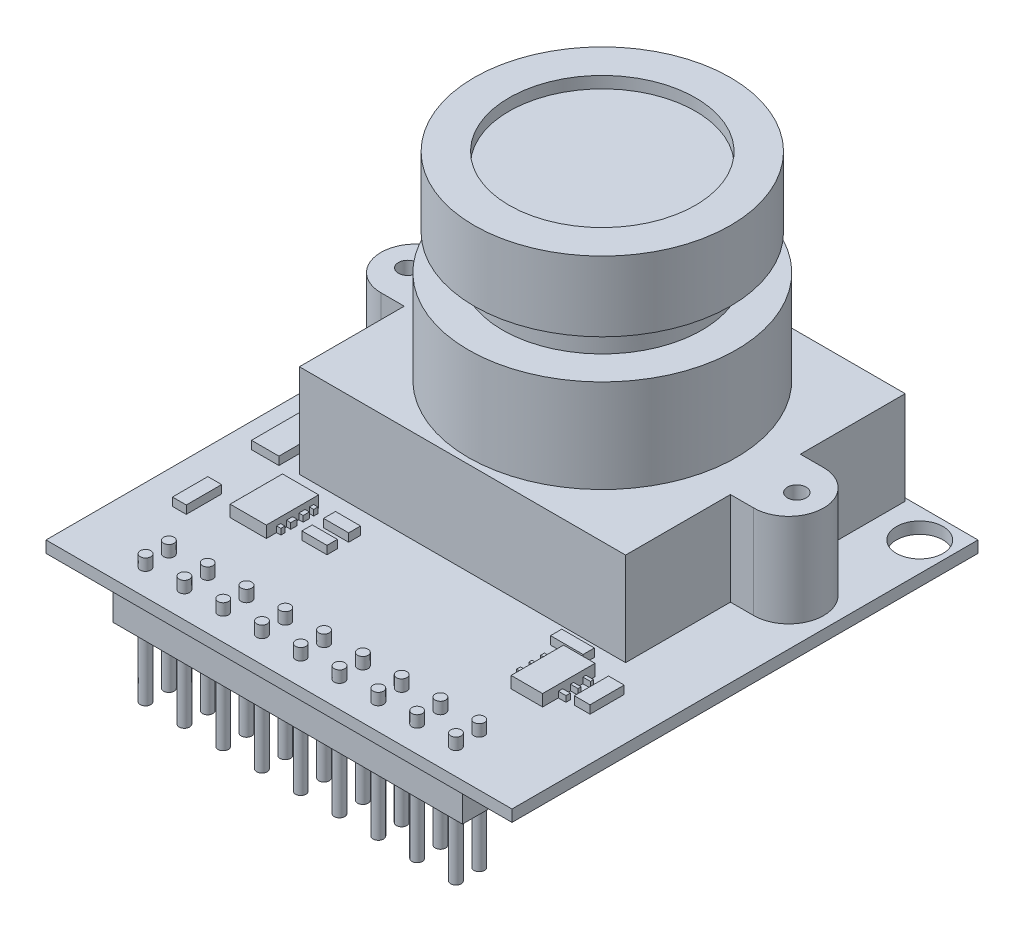
SolidWorks part; units mm, degrees
ref_plane "前视基准面" through (0, 0, 0) normal (0, 0, 1) x (1, 0, 0)
ref_plane "上视基准面" through (0, 0, 0) normal (0, 1, 0) x (1, 0, 0)
ref_plane "右视基准面" through (0, 0, 0) normal (1, 0, 0) x (0, 0, -1)
sketch "草图1" plane through (0, 0, 0) normal (0, 1, 0) x (1, 0, 0)
  line L1 (-20, 20) -> (20, 20)
  line L2 (-20, 20) -> (-20, -20)
  line L3 (-20, -20) -> (20, -20)
  line L4 (20, 20) -> (20, -20)
  line L5 (-20, 20) -> (20, -20) construction
  line L6 (-20, -20) -> (20, 20) construction
  point P0 (0, 0)
  dimension "D1" = 40
  dimension "D2" = 40
extrude "凸台-拉伸1" add sketch "草图1" along normal blind 1
sketch "草图2" plane through (0, 1, 0) normal (0, 1, 0) x (1, 0, 0)
  line L1 (-17.5, -17.5) -> (17.5, -17.5)
  line L2 (-17.5, -17.5) -> (-17.5, 17.5)
  line L3 (-17.5, 17.5) -> (17.5, 17.5)
  line L4 (17.5, -17.5) -> (17.5, 17.5)
  line L5 (-17.5, -17.5) -> (17.5, 17.5) construction
  line L6 (-17.5, 17.5) -> (17.5, -17.5) construction
  circle A0 centre (-17.5, 17.5) radius 2
  point P0 (0, 0)
  dimension "D1" = 4
  dimension "32" = 35
  dimension "D2" = 35
extrude "切除-拉伸1" cut sketch "草图2" against normal blind 1 contours L2 A0 L3 | L3 A0 L2 region at (-17.7829, 1, -17.7829) region at (-16.6512, 1, -16.6512)
mirror "镜向1" about plane through (0, 0, 0) normal (1, 0, 0) of "切除-拉伸1"
sketch "草图3" plane through (0, 1, 0) normal (0, 1, 0) x (1, 0, 0)
  line L0 (-16, 7.751) -> (16, 7.751) construction
  line L1 (-14, 19.751) -> (14, 19.751)
  line L2 (-14, 19.751) -> (-14, 10.751)
  line L3 (-14, -4.249) -> (14, -4.249)
  line L4 (14, 19.751) -> (14, 10.751)
  line L5 (-14, 19.751) -> (14, -4.249) construction
  line L6 (-14, -4.249) -> (14, 19.751) construction
  line L7 (-16, 10.751) -> (-14, 10.751)
  line L8 (-16, 4.751) -> (-14, 4.751)
  line L9 (14, 10.751) -> (16, 10.751)
  line L10 (-14, 4.751) -> (-14, -4.249)
  line L11 (14, 4.751) -> (16, 4.751)
  line L12 (14, 4.751) -> (14, -4.249)
  arc A0 (-16, 10.751) -> (-16, 4.751) centre (-16, 7.751) ccw
  arc A1 (16, 4.751) -> (16, 10.751) centre (16, 7.751) ccw
  point P0 (0, 7.751)
  point P8 (0, 7.751)
  dimension "D5" = 3
  dimension "D1" = 24
  dimension "D2" = 28
  dimension "D3" = 0
  dimension "D4" = 32
extrude "凸台-拉伸2" add sketch "草图3" along normal blind 8
sketch "草图4" plane through (0, 9, 0) normal (0, 1, 0) x (1, 0, 0)
  line L0 (16, 7.751) -> (-16, 7.751) construction
  circle A0 centre (0, 7.751) radius 11.5
  dimension "D1" = 23
extrude "凸台-拉伸3" add sketch "草图4" along normal blind 8
sketch "草图5" plane through (0, 17, 0) normal (0, 1, 0) x (1, 0, 0)
  circle A0 centre (0, 7.751) radius 8.5592
extrude "凸台-拉伸4" add sketch "草图5" along normal blind 3
sketch "草图6" plane through (0, 20, 0) normal (0, 1, 0) x (1, 0, 0)
  circle A0 centre (0, 7.751) radius 11
  dimension "D1" = 22
extrude "凸台-拉伸5" add sketch "草图6" along normal blind 6
sketch "草图7" plane through (0, 20, 0) normal (0, -1, 0) x (1, 0, 0)
  circle A0 centre (0, -7.751) radius 9.5297
extrude "凸台-拉伸6" add sketch "草图7" along normal blind 0.5
chamfer "倒角1" distance 0.5 angle 45 1 edges at (0, 19.5, -17.2807)
sketch "草图8" plane through (0, 26, 0) normal (0, 1, 0) x (1, 0, 0)
  circle A0 centre (0, 7.751) radius 9.9394
extrude "切除-拉伸2" cut sketch "草图8" against normal blind 4.5
sketch "草图9" plane through (0, 26, 0) normal (0, 1, 0) x (1, 0, 0)
  circle A1 centre (0, 7.751) radius 8
  circle A2 centre (0, 7.751) radius 9.9394
  circle A3 centre (0, 7.751) radius 9.9394
  dimension "D2" = 16
  dimension "D1" = 0
extrude "凸台-拉伸7" add sketch "草图9" against normal blind 1
sketch "草图10" plane through (0, 21.5, 0) normal (0, 1, 0) x (1, 0, 0)
  circle A0 centre (0, 7.751) radius 4
  dimension "D1" = 8
extrude "凸台-拉伸8" add sketch "草图10" along normal blind 1
fillet "圆角2" radius 0.8 1 edges at (0, 22.5, -3.751)
sketch "草图11" plane through (0, 21.5, 0) normal (0, 1, 0) x (1, 0, 0)
  circle A0 centre (0, 7.751) radius 6.0073
extrude "凸台-拉伸9" add sketch "草图11" along normal blind 0.5
sketch "草图12" plane through (0, 25, 0) normal (0, -1, 0) x (1, 0, 0)
  circle A0 centre (0, -7.751) radius 9.9394
extrude "凸台-拉伸10" add sketch "草图12" along normal blind 0.7
sketch "草图13" plane through (0, 1, 0) normal (0, 1, 0) x (1, 0, 0)
  line L1 (-17.8881, 1.2139) -> (-15.5351, 1.2139)
  line L2 (-17.8881, 1.2139) -> (-17.8881, -4.4725)
  line L3 (-17.8881, -4.4725) -> (-15.5351, -4.4725)
  line L4 (-15.5351, 1.2139) -> (-15.5351, -4.4725)
  line L5 (-17.8881, 1.2139) -> (-15.5351, -4.4725) construction
  line L6 (-17.8881, -4.4725) -> (-15.5351, 1.2139) construction
  line L7 (-8.9905, -6.1617) -> (-6.8378, -6.1617)
  line L8 (-8.9905, -6.1617) -> (-8.9905, -7.1842)
  line L9 (-8.9905, -7.1842) -> (-6.8378, -7.1842)
  line L10 (-6.8378, -6.1617) -> (-6.8378, -7.1842)
  line L11 (-8.9905, -6.1617) -> (-6.8378, -7.1842) construction
  line L12 (-8.9905, -7.1842) -> (-6.8378, -6.1617) construction
  line L13 (-8.9905, -8.1543) -> (-6.8378, -8.1543)
  line L14 (-8.9905, -8.1543) -> (-8.9905, -9.045)
  line L15 (-8.9905, -9.045) -> (-6.8378, -9.045)
  line L16 (-6.8378, -8.1543) -> (-6.8378, -9.045)
  line L17 (-8.9905, -8.1543) -> (-6.8378, -9.045) construction
  line L18 (-8.9905, -9.045) -> (-6.8378, -8.1543) construction
  line L19 (-17.0629, -9.045) -> (-15.879, -9.045)
  line L20 (-17.0629, -9.045) -> (-17.0629, -12.0815)
  line L21 (-17.0629, -12.0815) -> (-15.879, -12.0815)
  line L22 (-15.879, -9.045) -> (-15.879, -12.0815)
  line L23 (-17.0629, -9.045) -> (-15.879, -12.0815) construction
  line L24 (-17.0629, -12.0815) -> (-15.879, -9.045) construction
  line L25 (9.4685, -5.193) -> (12.267, -5.193)
  line L26 (9.4685, -5.193) -> (9.4685, -6.1617)
  line L27 (9.4685, -6.1617) -> (12.267, -6.1617)
  line L28 (12.267, -5.193) -> (12.267, -6.1617)
  line L29 (9.4685, -5.193) -> (12.267, -6.1617) construction
  line L30 (9.4685, -6.1617) -> (12.267, -5.193) construction
  line L31 (14.9578, -6.673) -> (16.3032, -6.673)
  line L32 (14.9578, -6.673) -> (14.9578, -9.6059)
  line L33 (14.9578, -9.6059) -> (16.3032, -9.6059)
  line L34 (16.3032, -6.673) -> (16.3032, -9.6059)
  line L35 (14.9578, -6.673) -> (16.3032, -9.6059) construction
  line L36 (14.9578, -9.6059) -> (16.3032, -6.673) construction
  point P4 (-16.7116, -1.6293)
  point P9 (-7.9142, -6.673)
  point P14 (-7.9142, -8.5997)
  point P19 (-16.471, -10.5633)
  point P24 (10.8677, -5.6774)
  point P29 (15.6305, -8.1395)
extrude "凸台-拉伸11" add sketch "草图13" along normal blind 0.7
sketch "草图14" plane through (0, 1, 0) normal (0, 1, 0) x (1, 0, 0)
  line L1 (-13.7569, -5.9438) -> (-10.649, -5.9438)
  line L2 (-13.7569, -5.9438) -> (-13.7569, -10.4364)
  line L3 (-13.7569, -10.4364) -> (-10.649, -10.4364)
  line L4 (-10.649, -5.9438) -> (-10.649, -10.4364)
  line L5 (-13.7569, -5.9438) -> (-10.649, -10.4364) construction
  line L6 (-13.7569, -10.4364) -> (-10.649, -5.9438) construction
  line L7 (11.0319, -6.6059) -> (13.7329, -6.6059)
  line L8 (11.0319, -6.6059) -> (11.0319, -11.1075)
  line L9 (11.0319, -11.1075) -> (13.7329, -11.1075)
  line L10 (13.7329, -6.6059) -> (13.7329, -11.1075)
  line L11 (11.0319, -6.6059) -> (13.7329, -11.1075) construction
  line L12 (11.0319, -11.1075) -> (13.7329, -6.6059) construction
  point P4 (-12.203, -8.1901)
  point P9 (12.3824, -8.8567)
extrude "凸台-拉伸12" add sketch "草图14" along normal blind 1
sketch "草图15" plane through (0, 1, 0) normal (0, 1, 0) x (1, 0, 0)
  line L0 (-13.7569, -5.9438) -> (-13.7569, -10.4364) construction
  line L1 (-14.2644, -6.5646) -> (-13.7569, -6.5646)
  line L2 (-14.2644, -6.5646) -> (-14.2644, -6.9193)
  line L3 (-14.2644, -6.9193) -> (-13.7569, -6.9193)
  line L4 (-13.7569, -6.5646) -> (-13.7569, -6.9193)
  line L5 (-14.2644, -6.5646) -> (-13.7569, -6.9193) construction
  line L6 (-14.2644, -6.9193) -> (-13.7569, -6.5646) construction
  line L7 (-13.7569, -5.9438) -> (-13.7569, -10.4364) construction
  line L8 (-14.2644, -7.4617) -> (-13.7569, -7.4617)
  line L9 (-14.2644, -7.4617) -> (-14.2644, -7.8372)
  line L10 (-14.2644, -7.8372) -> (-13.7569, -7.8372)
  line L11 (-13.7569, -7.4617) -> (-13.7569, -7.8372)
  line L12 (-14.2644, -7.4617) -> (-13.7569, -7.8372) construction
  line L13 (-14.2644, -7.8372) -> (-13.7569, -7.4617) construction
  line L14 (-14.2644, -8.523) -> (-13.7569, -8.523)
  line L15 (-14.2644, -8.523) -> (-14.2644, -8.9011)
  line L16 (-14.2644, -8.9011) -> (-13.7569, -8.9011)
  line L17 (-13.7569, -8.523) -> (-13.7569, -8.9011)
  line L18 (-14.2644, -8.523) -> (-13.7569, -8.9011) construction
  line L19 (-14.2644, -8.9011) -> (-13.7569, -8.523) construction
  line L20 (-10.649, -10.4364) -> (-10.649, -5.9438) construction
  line L21 (-14.2644, -9.36) -> (-13.7569, -9.36)
  line L22 (-14.2644, -9.36) -> (-14.2644, -9.7564)
  line L23 (-14.2644, -9.7564) -> (-13.7569, -9.7564)
  line L24 (-13.7569, -9.36) -> (-13.7569, -9.7564)
  line L25 (-14.2644, -9.36) -> (-13.7569, -9.7564) construction
  line L26 (-14.2644, -9.7564) -> (-13.7569, -9.36) construction
  line L27 (-10.649, -6.3769) -> (-10.2799, -6.3769)
  line L28 (-10.649, -6.3769) -> (-10.649, -6.7419)
  line L29 (-10.649, -6.7419) -> (-10.2799, -6.7419)
  line L30 (-10.2799, -6.3769) -> (-10.2799, -6.7419)
  line L31 (-10.649, -6.3769) -> (-10.2799, -6.7419) construction
  line L32 (-10.649, -6.7419) -> (-10.2799, -6.3769) construction
  line L33 (-10.649, -10.4364) -> (-10.649, -5.9438) construction
  line L34 (-10.649, -7.1151) -> (-10.2799, -7.1151)
  line L35 (-10.649, -7.1151) -> (-10.649, -7.6494)
  line L36 (-10.649, -7.6494) -> (-10.2799, -7.6494)
  line L37 (-10.2799, -7.1151) -> (-10.2799, -7.6494)
  line L38 (-10.649, -7.1151) -> (-10.2799, -7.6494) construction
  line L39 (-10.649, -7.6494) -> (-10.2799, -7.1151) construction
  line L40 (13.7329, -11.1075) -> (13.7329, -6.6059) construction
  line L41 (-10.649, -8.1901) -> (-10.2799, -8.1901)
  line L42 (-10.649, -8.1901) -> (-10.649, -8.7121)
  line L43 (-10.649, -8.7121) -> (-10.2799, -8.7121)
  line L44 (-10.2799, -8.1901) -> (-10.2799, -8.7121)
  line L45 (-10.649, -8.1901) -> (-10.2799, -8.7121) construction
  line L46 (-10.649, -8.7121) -> (-10.2799, -8.1901) construction
  line L47 (-10.649, -9.214) -> (-10.2799, -9.214)
  line L48 (-10.649, -9.214) -> (-10.649, -9.5582)
  line L49 (-10.649, -9.5582) -> (-10.2799, -9.5582)
  line L50 (-10.2799, -9.214) -> (-10.2799, -9.5582)
  line L51 (-10.649, -9.214) -> (-10.2799, -9.5582) construction
  line L52 (-10.649, -9.5582) -> (-10.2799, -9.214) construction
  line L53 (13.7329, -7.3823) -> (14.3886, -7.3823)
  line L54 (13.7329, -7.3823) -> (13.7329, -7.6494)
  line L55 (13.7329, -7.6494) -> (14.3886, -7.6494)
  line L56 (14.3886, -7.3823) -> (14.3886, -7.6494)
  line L57 (13.7329, -7.3823) -> (14.3886, -7.6494) construction
  line L58 (13.7329, -7.6494) -> (14.3886, -7.3823) construction
  line L59 (11.0319, -6.6059) -> (11.0319, -11.1075) construction
  line L60 (13.7329, -8.4511) -> (14.3886, -8.4511)
  line L61 (13.7329, -8.4511) -> (13.7329, -8.7121)
  line L62 (13.7329, -8.7121) -> (14.3886, -8.7121)
  line L63 (14.3886, -8.4511) -> (14.3886, -8.7121)
  line L64 (13.7329, -8.4511) -> (14.3886, -8.7121) construction
  line L65 (13.7329, -8.7121) -> (14.3886, -8.4511) construction
  line L66 (13.7329, -9.3861) -> (14.3886, -9.3861)
  line L67 (13.7329, -9.3861) -> (13.7329, -9.7564)
  line L68 (13.7329, -9.7564) -> (14.3886, -9.7564)
  line L69 (14.3886, -9.3861) -> (14.3886, -9.7564)
  line L70 (13.7329, -9.3861) -> (14.3886, -9.7564) construction
  line L71 (13.7329, -9.7564) -> (14.3886, -9.3861) construction
  line L72 (10.2993, -7.5158) -> (11.0319, -7.5158)
  line L73 (10.2993, -7.5158) -> (10.2993, -7.8372)
  line L74 (10.2993, -7.8372) -> (11.0319, -7.8372)
  line L75 (11.0319, -7.5158) -> (11.0319, -7.8372)
  line L76 (10.2993, -7.5158) -> (11.0319, -7.8372) construction
  line L77 (10.2993, -7.8372) -> (11.0319, -7.5158) construction
  line L79 (10.2993, -8.5816) -> (11.0319, -8.5816)
  line L80 (10.2993, -8.5816) -> (10.2993, -8.8567)
  line L81 (10.2993, -8.8567) -> (11.0319, -8.8567)
  line L82 (11.0319, -8.5816) -> (11.0319, -8.8567)
  line L83 (10.2993, -8.5816) -> (11.0319, -8.8567) construction
  line L84 (10.2993, -8.8567) -> (11.0319, -8.5816) construction
  line L85 (10.2993, -9.5713) -> (11.0319, -9.5713)
  line L86 (10.2993, -9.5713) -> (10.2993, -9.9097)
  line L87 (10.2993, -9.9097) -> (11.0319, -9.9097)
  line L88 (11.0319, -9.5713) -> (11.0319, -9.9097)
  line L89 (10.2993, -9.5713) -> (11.0319, -9.9097) construction
  line L90 (10.2993, -9.9097) -> (11.0319, -9.5713) construction
  point P4 (-14.0107, -6.7419)
  point P11 (-14.0107, -7.6494)
  point P16 (-14.0107, -8.7121)
  point P23 (-14.0107, -9.5582)
  point P28 (-10.4645, -6.5594)
  point P35 (-10.4645, -7.3823)
  point P42 (-10.4645, -8.4511)
  point P47 (-10.4645, -9.3861)
  point P52 (14.0607, -7.5158)
  point P59 (14.0607, -8.5816)
  point P64 (14.0607, -9.5713)
  point P69 (10.6656, -7.6765)
  point P76 (10.6656, -8.7191)
  point P81 (10.6656, -9.7405)
extrude "凸台-拉伸13" add sketch "草图15" along normal blind 0.5
sketch "草图16" plane through (0, 0, 0) normal (0, -1, 0) x (1, 0, 0)
  line L0 (-14, -4.751) -> (-14, -10.751)
  line L1 (14, -4.751) -> (14, -10.751)
  line L10 (14, -4.751) -> (14, 4.249)
  line L11 (16, -4.751) -> (14, -4.751)
  line L12 (14, -10.751) -> (16, -10.751)
  line L13 (14, -19.751) -> (14, -10.751)
  line L14 (-14, -19.751) -> (14, -19.751)
  line L15 (-14, -10.751) -> (-14, -19.751)
  line L16 (-16, -10.751) -> (-14, -10.751)
  line L17 (-14, -4.751) -> (-16, -4.751)
  line L18 (-14, 4.249) -> (-14, -4.751)
  line L19 (14, 4.249) -> (-14, 4.249)
  line L20 (14, -4.751) -> (14, 4.249)
  line L23 (14, -19.751) -> (14, -10.751)
  line L24 (-14, -19.751) -> (14, -19.751)
  line L25 (-14, -10.751) -> (-14, -19.751)
  line L28 (-14, 4.249) -> (-14, -4.751)
  line L29 (14, 4.249) -> (-14, 4.249)
  arc A2 (16, -10.751) -> (16, -4.751) centre (16, -7.751) ccw
  arc A3 (-16, -4.751) -> (-16, -10.751) centre (-16, -7.751) ccw
  dimension "D1" = 0
extrude "凸台-拉伸14" add sketch "草图16" along normal blind 0.1
sketch "草图17" plane through (0, 0, 0) normal (0, -1, 0) x (1, 0, 0)
  line L8 (20, -20) -> (20, 20)
  line L9 (20, 20) -> (-20, 20)
  line L10 (-20, 20) -> (-20, -20)
  line L11 (-20, -20) -> (20, -20)
  line L12 (20, -20) -> (20, 20)
  line L13 (20, 20) -> (-20, 20)
  line L14 (-20, 20) -> (-20, -20)
  line L15 (-20, -20) -> (20, -20)
  arc A0 (-16, -4.751) -> (-16, -10.751) centre (-16, -7.751) ccw construction
  arc A1 (-16, -4.751) -> (-16, -10.751) centre (-16, -7.751) ccw
  circle A2 centre (-16.6368, -7.751) radius 1.9945
  dimension "D1" = 0
extrude "凸台-拉伸15" add sketch "草图17" along normal blind 1 contours A2 region at (-16.6368, 0, -7.751)
mirror "镜向2" about plane through (0, 0, 0) normal (1, 0, 0) of "凸台-拉伸15"
sketch "草图18" plane through (0, -1, 0) normal (0, -1, 0) x (1, 0, 0)
  line L0 (-17.0588, -5.8017) -> (-17.0588, -7.3261)
  line L1 (-17.0588, -7.3261) -> (-18.5854, -7.3261)
  line L2 (-18.5854, -8.1759) -> (-17.0588, -8.1759)
  line L3 (-17.0588, -8.1759) -> (-17.0588, -9.7003)
  line L4 (-16.2147, -5.8017) -> (-16.2147, -7.3261)
  line L5 (-16.2147, -7.3261) -> (-14.6881, -7.3261)
  line L6 (-16.2147, -9.7003) -> (-16.2147, -8.1759)
  line L7 (-16.2147, -8.1759) -> (-14.6881, -8.1759)
  circle A0 centre (-16.6368, -7.751) radius 1.9945 construction
  circle A1 centre (-16.6368, -7.751) radius 1.9945 construction
  circle A2 centre (-16.6368, -7.751) radius 1.9945
  circle M1 centre (-16.6368, -7.751) radius 1.9945
extrude "切除-拉伸3" cut sketch "草图18" against normal blind 0.2 contours L6 L7 L5 L4 L0 L1 L2 L3 M1 region at (-16.6368, -1, -7.751)
mirror "镜向3" about plane through (0, 0, 0) normal (1, 0, 0) of "切除-拉伸3"
sketch "草图19" plane through (0, 0, 0) normal (1, 0, 0) x (0, 0, -1)
  line L0 (7.751, 22.5) -> (7.751, -2.0724) construction
  line L2 (7.751, 18.763) -> (7.751, 23.6327)
  arc A0 (7.751, 23.6327) -> (7.751, 18.763) centre (7.751, 21.1978) ccw
revolve "旋转1" add sketch "草图19" angle 360 about L0
sketch "草图20" plane through (0, 0, 0) normal (0, -1, 0) x (1, 0, 0)
  line L0 (14, 4.249) -> (-14, 4.249) construction
  line L1 (-15, 19.249) -> (15, 19.249)
  line L2 (-15, 19.249) -> (-15, 14.249)
  line L3 (-15, 14.249) -> (15, 14.249)
  line L4 (15, 19.249) -> (15, 14.249)
  line L5 (-15, 19.249) -> (15, 14.249) construction
  line L6 (-15, 14.249) -> (15, 19.249) construction
  point P0 (0, 16.749)
  dimension "D1" = 10
  dimension "D2" = 5
  dimension "D3" = 30
  dimension "D4" = 0
extrude "凸台-拉伸16" add sketch "草图20" along normal blind 3
sketch "草图21" plane through (0, -3, 0) normal (0, -1, 0) x (1, 0, 0)
  line L0 (-15, 14.249) -> (15, 14.249) construction
  line L1 (15, 19.249) -> (-15, 19.249) construction
  circle A0 centre (-13.7029, 17.749) radius 0.45
  circle A1 centre (-13.7029, 15.749) radius 0.45
  circle A2 centre (-10.3729, 15.749) radius 0.45
  circle A3 centre (-10.3729, 17.749) radius 0.45
  circle A4 centre (-7.0429, 15.749) radius 0.45
  circle A5 centre (-7.0429, 17.749) radius 0.45
  circle A6 centre (-3.7129, 15.749) radius 0.45
  circle A7 centre (-3.7129, 17.749) radius 0.45
  circle A8 centre (-0.3829, 15.749) radius 0.45
  circle A9 centre (-0.3829, 17.749) radius 0.45
  circle A10 centre (2.9471, 15.749) radius 0.45
  circle A11 centre (2.9471, 17.749) radius 0.45
  circle A12 centre (6.2771, 15.749) radius 0.45
  circle A13 centre (6.2771, 17.749) radius 0.45
  circle A14 centre (9.6071, 15.749) radius 0.45
  circle A15 centre (9.6071, 17.749) radius 0.45
  circle A16 centre (12.9371, 15.749) radius 0.45
  circle A17 centre (12.9371, 17.749) radius 0.45
  dimension "D1" = 0.9
  dimension "D2" = 0.9
  dimension "D3" = 1.5
  dimension "D4" = 1.5
  dimension "D5" = 9
extrude "凸台-拉伸17" add sketch "草图21" along normal blind 6
sketch "草图22" plane through (0, -3, 0) normal (0, -1, 0) x (1, 0, 0)
  circle A0 centre (12.9371, 17.749) radius 0.45 construction
  circle A1 centre (12.9371, 15.749) radius 0.45 construction
  circle A2 centre (9.6071, 15.749) radius 0.45 construction
  circle A3 centre (9.6071, 17.749) radius 0.45 construction
  circle A4 centre (6.2771, 17.749) radius 0.45 construction
  circle A5 centre (6.2771, 15.749) radius 0.45 construction
  circle A6 centre (-0.3829, 15.749) radius 0.45 construction
  circle A7 centre (2.9471, 15.749) radius 0.45 construction
  circle A8 centre (2.9471, 17.749) radius 0.45 construction
  circle A9 centre (-0.3829, 17.749) radius 0.45 construction
  circle A10 centre (-3.7129, 15.749) radius 0.45 construction
  circle A11 centre (-3.7129, 17.749) radius 0.45 construction
  circle A12 centre (-7.0429, 15.749) radius 0.45 construction
  circle A13 centre (-7.0429, 17.749) radius 0.45 construction
  circle A14 centre (-10.3729, 15.749) radius 0.45 construction
  circle A15 centre (-10.3729, 17.749) radius 0.45 construction
  circle A16 centre (-13.7029, 15.749) radius 0.45 construction
  circle A17 centre (-13.7029, 17.749) radius 0.45 construction
  circle A18 centre (-3.7129, 15.749) radius 0.45 construction
  circle A19 centre (-7.0429, 15.749) radius 0.45 construction
  circle A20 centre (12.9371, 17.749) radius 0.45
  circle A21 centre (12.9371, 15.749) radius 0.45
  circle A22 centre (9.6071, 15.749) radius 0.45
  circle A23 centre (9.6071, 17.749) radius 0.45
  circle A24 centre (6.2771, 17.749) radius 0.45
  circle A25 centre (6.2771, 15.749) radius 0.45
  circle A26 centre (-0.3829, 15.749) radius 0.45
  circle A27 centre (2.9471, 15.749) radius 0.45
  circle A28 centre (2.9471, 17.749) radius 0.45
  circle A29 centre (-0.3829, 17.749) radius 0.45
  circle A30 centre (-3.7129, 15.749) radius 0.45
  circle A31 centre (-3.7129, 17.749) radius 0.45
  circle A32 centre (-7.0429, 15.749) radius 0.45
  circle A33 centre (-7.0429, 17.749) radius 0.45
  circle A34 centre (-10.3729, 15.749) radius 0.45
  circle A35 centre (-10.3729, 17.749) radius 0.45
  circle A36 centre (-13.7029, 15.749) radius 0.45
  circle A37 centre (-13.7029, 17.749) radius 0.45
  circle A38 centre (-3.7129, 15.749) radius 0.45
  circle A39 centre (-7.0429, 15.749) radius 0.45
extrude "凸台-拉伸18" add sketch "草图22" against normal blind 5 contours A37 | A36 | A34 | A35 | A33 | A32 | A31 | A30 | A29 | A26 | A28 | A27 | A24 | A23 | A20 | A21 | A22 | A25
sketch "草图23" plane through (0, 9, 0) normal (0, 1, 0) x (1, 0, 0)
  circle A0 centre (16.6975, 7.751) radius 0.8031
extrude "切除-拉伸4" cut sketch "草图23" against normal up to surface (8 mm away) up to face at (6.2771, 1, 16.199)
mirror "镜向4" about plane through (0, 0, 0) normal (1, 0, 0) of "切除-拉伸4"
scale "缩放比例1" bodies to scale 132 scale about origin uniform scaling yes scale factor 0.6
